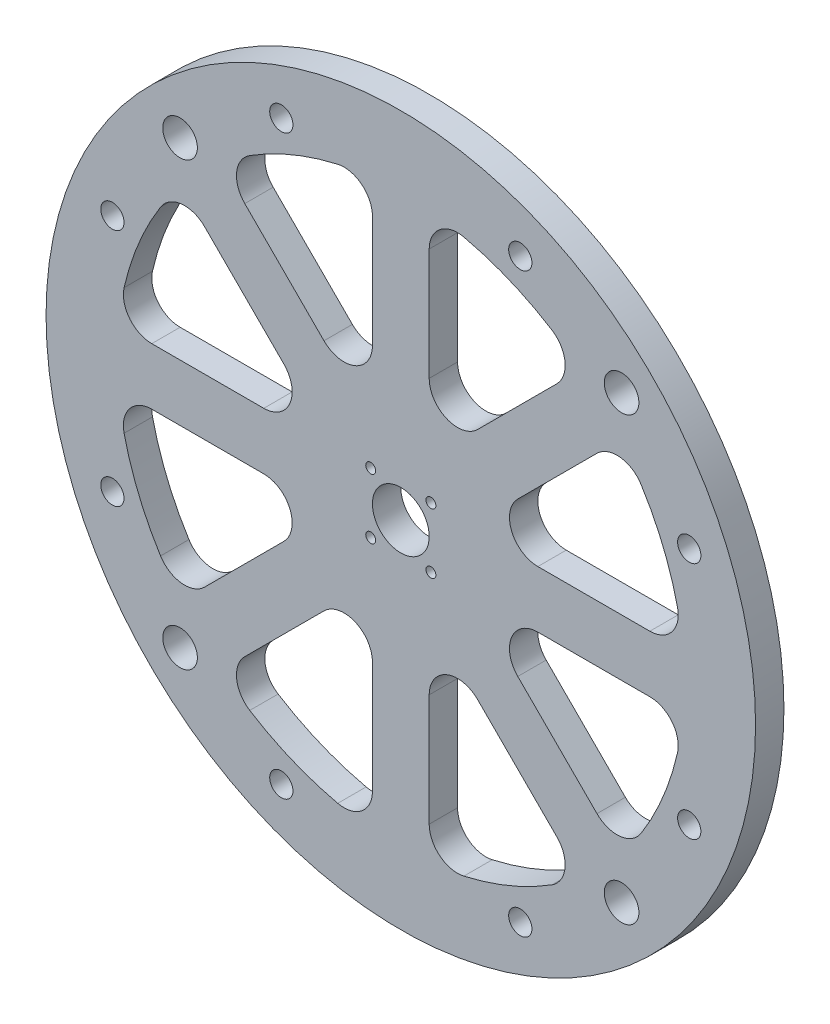
SolidWorks part; units mm, degrees
ref_plane "Front" through (0, 0, 0) normal (0, 0, 1) x (1, 0, 0)
ref_plane "Top" through (0, 0, 0) normal (0, 1, 0) x (1, 0, 0)
ref_plane "Right" through (0, 0, 0) normal (1, 0, 0) x (0, 0, -1)
sketch "Sketch1" plane through (0, 0, 0) normal (0, 0, 1) x (1, 0, 0)
  line L0 (0, 0) -> (77.7817, 77.7817) construction
  line L1 (0, 0) -> (206.6736, 0) construction
  line L2 (0, 0) -> (101.6267, 42.0952) construction
  line L3 (0, 0) -> (42.0952, 101.6267) construction
  line L4 (0, 0) -> (0, 161.9179) construction
  circle A0 centre (0, 0) radius 125
  circle A1 centre (77.7817, 77.7817) radius 6.1
  circle A2 centre (0, 0) radius 110 construction
  circle A3 centre (101.6267, 42.0952) radius 4.1
  circle A4 centre (42.0952, 101.6267) radius 4.1
  circle A5 centre (101.6267, -42.0952) radius 4.1
  circle A6 centre (77.7817, -77.7817) radius 6.1
  circle A7 centre (42.0952, -101.6267) radius 4.1
  circle A8 centre (-42.0952, -101.6267) radius 4.1
  circle A9 centre (-77.7817, -77.7817) radius 6.1
  circle A10 centre (-101.6267, -42.0952) radius 4.1
  circle A11 centre (-101.6267, 42.0952) radius 4.1
  circle A12 centre (-77.7817, 77.7817) radius 6.1
  circle A13 centre (-42.0952, 101.6267) radius 4.1
  point P11 (77.7817, -77.7817)
  point P12 (0, 0)
  point P33 (0, 0)
  dimension "D1" = 250
  dimension "D2" = 12.2
  dimension "D4" = 220
  dimension "D5" = 8.2
  dimension "D7" = 22.5
  dimension "D3" = 45
  dimension "D6" = 22.5
  dimension "D8" = 4
extrude "Boss-Extrude1" add sketch "Sketch1" along normal blind 10
sketch "Sketch2" plane through (0, 0, 0) normal (0, 0, 1) x (1, 0, 0)
  line L0 (0, 0) -> (0, 164.9961) construction
  line L1 (-166.1808, 0) -> (215.2356, 0) construction
  line L2 (-10, 24.1421) -> (-10, 99.4987)
  line L3 (0, 0) -> (10.6066, 10.6066) construction
  line L4 (10, 24.1421) -> (10, 99.4987)
  line L5 (24.1421, 10) -> (77.4273, 63.2852)
  line L6 (10, 24.1421) -> (63.2852, 77.4273)
  line L7 (24.1421, -10) -> (99.4987, -10)
  line L8 (24.1421, 10) -> (99.4987, 10)
  line L9 (10, -24.1421) -> (63.2852, -77.4273)
  line L10 (24.1421, -10) -> (77.4273, -63.2852)
  line L11 (-10, -24.1421) -> (-10, -99.4987)
  line L12 (10, -24.1421) -> (10, -99.4987)
  line L13 (-24.1421, -10) -> (-77.4273, -63.2852)
  line L14 (-10, -24.1421) -> (-63.2852, -77.4273)
  line L15 (-24.1421, 10) -> (-99.4987, 10)
  line L16 (-24.1421, -10) -> (-99.4987, -10)
  line L17 (-10, 24.1421) -> (-63.2852, 77.4273)
  line L18 (-24.1421, 10) -> (-77.4273, 63.2852)
  circle A0 centre (0, 0) radius 110 construction
  circle A1 centre (0, 0) radius 100
  circle A2 centre (0, 0) radius 10
  circle A3 centre (0, 0) radius 15 construction
  circle A4 centre (0, 0) radius 20
  circle A5 centre (10.6066, 10.6066) radius 1.75
  circle A9 centre (10.6066, -10.6066) radius 1.75
  circle A10 centre (-10.6066, -10.6066) radius 1.75
  circle A11 centre (-10.6066, 10.6066) radius 1.75
  point P25 (0, 0)
  point P27 (40.7927, 6.7958)
  point P28 (0, 0)
  point P30 (63.2852, 77.4273)
  point P34 (77.4273, 63.2852)
  point P38 (99.4987, -10)
  point P42 (99.4987, 10)
  point P46 (77.4273, -63.2852)
  point P50 (63.2852, -77.4273)
  point P54 (10, -99.4987)
  point P58 (0, 0)
  point P59 (-10, -99.4987)
  point P60 (-63.2852, -77.4273)
  point P61 (-77.4273, -63.2852)
  point P62 (-99.4987, -10)
  point P63 (-99.4987, 10)
  point P64 (-77.4273, 63.2852)
  point P65 (-63.2852, 77.4273)
  dimension "D1" = 10
  dimension "D2" = 20
  dimension "D3" = 30
  dimension "D4" = 40
  dimension "D5" = 3.5
  dimension "D6" = 4
  dimension "D7" = 45
  dimension "D8" = 20
  dimension "D9" = 8
extrude "Cut-Extrude2" cut sketch "Sketch2" against normal through all both and the other way through all contours L2 A1 L17 | L6 A1 L4 | L8 A1 L5 | L10 A1 L7 | L12 A1 L9 | L14 A1 L11 | L16 A1 L13 | L18 A1 L15 region at (-28.4818, 68.7612, 0) region at (28.4818, 68.7612, 0) region at (-68.7612, 28.4818, 0) region at (68.7612, 28.4818, 0) region at (-68.7612, -28.4818, 0) region at (-28.4818, -68.7612, 0) region at (68.7612, -28.4818, 0) region at (28.4818, -68.7612, 0)
fillet "Fillet1" radius 10 24 edges at (-99.4987, 10, 5) (-77.4273, 63.2852, 5) (-24.1421, 10, 5) (-10, -99.4987, 5) (-63.2852, -77.4273, 5) (-10, -24.1421, 5) (-77.4273, -63.2852, 5) (-99.4987, -10, 5) (-24.1421, -10, 5) (99.4987, -10, 5) (77.4273, -63.2852, 5) (24.1421, -10, 5) (63.2852, -77.4273, 5) (10, -99.4987, 5) (10, -24.1421, 5) (10, 99.4987, 5) (63.2852, 77.4273, 5) (10, 24.1421, 5) (77.4273, 63.2852, 5) (99.4987, 10, 5) (24.1421, 10, 5) (-63.2852, 77.4273, 5) (-10, 99.4987, 5) (-10, 24.1421, 5)
extrude "Cut-Extrude3" cut sketch "Sketch2<4>" against normal through all both and the other way through all contours A5 | A11 | A10 | A9 | A2 region at (0, 0, 0) region at (10.6066, 10.6066, 0) region at (10.6066, -10.6066, 0) region at (-10.6066, -10.6066, 0) region at (-10.6066, 10.6066, 0)
sketch "Sketch2<4>" plane through (0, 0, 0) normal (0, 0, 1) x (1, 0, 0) same geometry as "Sketch2"
